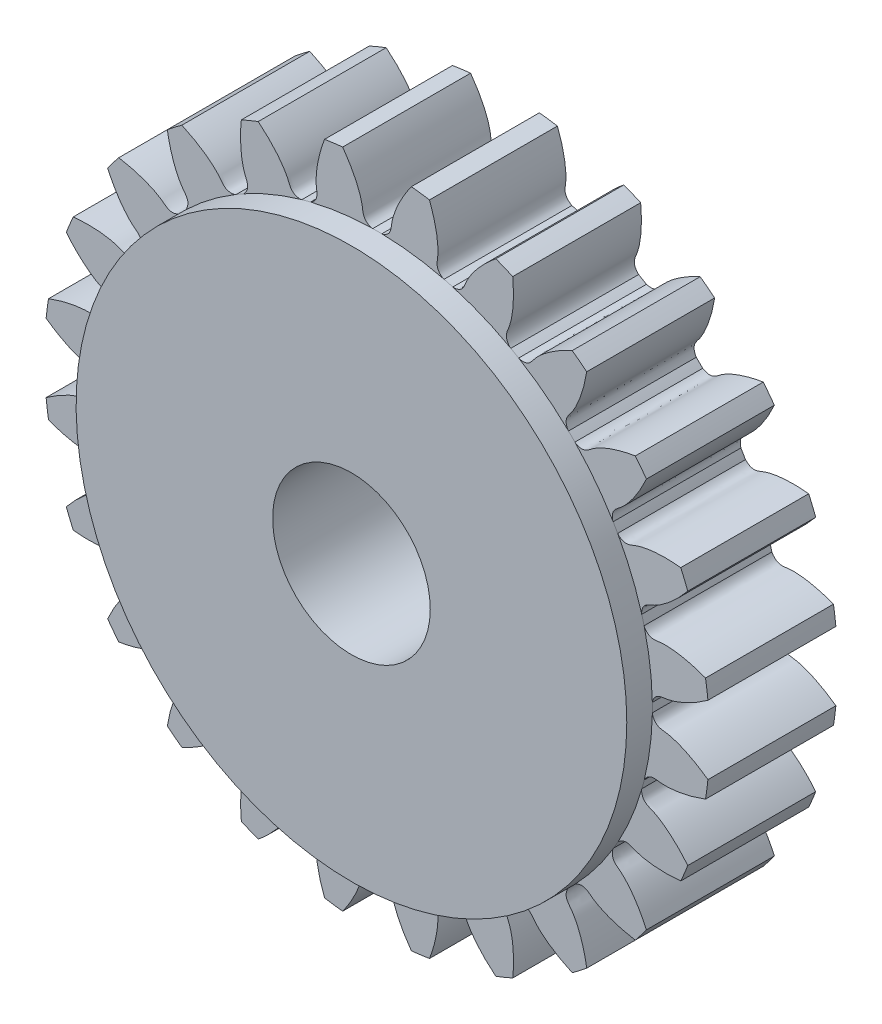
SolidWorks part; units mm, degrees
ref_plane "前视基准面" through (0, 0, 0) normal (0, 0, 1) x (1, 0, 0)
ref_plane "上视基准面" through (0, 0, 0) normal (0, 1, 0) x (1, 0, 0)
ref_plane "右视基准面" through (0, 0, 0) normal (1, 0, 0) x (0, 0, -1)
other "Configuration Table"
sketch "草图1" plane through (0, 0, 0) normal (0, 0, 1) x (1, 0, 0)
  circle A0 centre (0, 0) radius 6.5
extrude "凸台-拉伸1" add sketch "草图1" along normal blind 2.5
ref_axis "基准轴1" through (0, 0, 2.5) along (0, 0, -1)
sketch "草图2" plane through (0, 0, 0) normal (0, 0, 1) x (1, 0, 0)
  line L0 (0, 0) -> (0, 6.5) construction
  circle A0 centre (0, 0) radius 6.5 construction
  arc A1 (0.0884, 5.3743) -> (-0.0884, 5.3743) centre (0, 0) ccw
  arc A2 (1.5578, 7.3471) -> (-1.5578, 7.3471) centre (0, 0) ccw
  spline S0 degree 3 poles (0.0884, 5.3743) (0.284, 5.4284) (0.2695, 5.5579) (0.2931, 5.6863) (0.2965, 5.7029) (0.3007, 5.7216) (0.3058, 5.7424) (0.312, 5.7653) (0.3191, 5.7902) (0.3275, 5.8171) (0.3371, 5.846) (0.348, 5.8769) (0.3604, 5.9096) (0.3742, 5.9441) (0.3896, 5.9805) (0.4067, 6.0185) (0.4254, 6.0583) (0.446, 6.0997) (0.4684, 6.1427) (0.4928, 6.1872) (0.5192, 6.2332) (0.5476, 6.2806) (0.5782, 6.3293) (0.611, 6.3792) (0.6461, 6.4304) (0.6834, 6.4827) (0.7232, 6.536) (0.7654, 6.5903) (0.8101, 6.6456) (0.8574, 6.7016) (0.9073, 6.7583) (0.9598, 6.8158) (1.015, 6.8738) (1.0729, 6.9322) (1.1336, 6.9911) (1.1972, 7.0503) (1.2635, 7.1097) (1.3328, 7.1693) (1.4302, 7.2497) (1.506, 7.3084) (1.5578, 7.3471) knots 0 0 0 0 0.143961 0.149818 0.156577 0.164236 0.172796 0.182258 0.19262 0.203884 0.216049 0.229115 0.243082 0.25795 0.273719 0.290389 0.30796 0.326433 0.345806 0.366081 0.387257 0.409333 0.432311 0.45619 0.48097 0.506651 0.533234 0.560717 0.589101 0.618387 0.648574 0.679661 0.71165 0.74454 0.778331 0.813023 0.848616 0.885111 0.922506 1 1 1 1
  spline S1 degree 3 poles (-0.0884, 5.3743) (-0.284, 5.4284) (-0.2695, 5.5579) (-0.2931, 5.6863) (-0.2965, 5.7029) (-0.3007, 5.7216) (-0.3058, 5.7424) (-0.312, 5.7653) (-0.3191, 5.7902) (-0.3275, 5.8171) (-0.3371, 5.846) (-0.348, 5.8769) (-0.3604, 5.9096) (-0.3742, 5.9441) (-0.3896, 5.9805) (-0.4067, 6.0185) (-0.4254, 6.0583) (-0.446, 6.0997) (-0.4684, 6.1427) (-0.4928, 6.1872) (-0.5192, 6.2332) (-0.5476, 6.2806) (-0.5782, 6.3293) (-0.611, 6.3792) (-0.6461, 6.4304) (-0.6834, 6.4827) (-0.7232, 6.536) (-0.7654, 6.5903) (-0.8101, 6.6456) (-0.8574, 6.7016) (-0.9073, 6.7583) (-0.9598, 6.8158) (-1.015, 6.8738) (-1.0729, 6.9322) (-1.1336, 6.9911) (-1.1972, 7.0503) (-1.2635, 7.1097) (-1.3328, 7.1693) (-1.4302, 7.2497) (-1.506, 7.3084) (-1.5578, 7.3471) knots 0 0 0 0 0.143961 0.149818 0.156577 0.164236 0.172796 0.182258 0.19262 0.203884 0.216049 0.229115 0.243082 0.25795 0.273719 0.290389 0.30796 0.326433 0.345806 0.366081 0.387257 0.409333 0.432311 0.45619 0.48097 0.506651 0.533234 0.560717 0.589101 0.618387 0.648574 0.679661 0.71165 0.74454 0.778331 0.813023 0.848616 0.885111 0.922506 1 1 1 1
extrude "切除-拉伸1" cut sketch "草图2" along normal through all
pattern_circular "阵列(圆周)1" count 24 every 15 about axis through (0, 0, 2.5) along (0, 0, -1) of "切除-拉伸1"
sketch "草图3" plane through (0, 0, 0) normal (0, 0, 1) x (1, 0, 0)
  circle A0 centre (0, 0) radius 6 construction
  dimension "Dn" = 12
sketch "草图6" plane through (0, 0, 2.5) normal (0, 0, 1) x (1, 0, 0)
  circle A0 centre (0, 0) radius 5.38
  dimension "D1" = 10.76
extrude "凸台-拉伸2" add sketch "草图6" along normal blind 0.5
sketch "草图4" plane through (0, 0, 2.5) normal (0, 0, 1) x (1, 0, 0)
  circle A0 centre (0, 0) radius 1.54
  dimension "D1" = 3.08
extrude "切除-拉伸2" cut sketch "草图4" against normal mid plane 10
